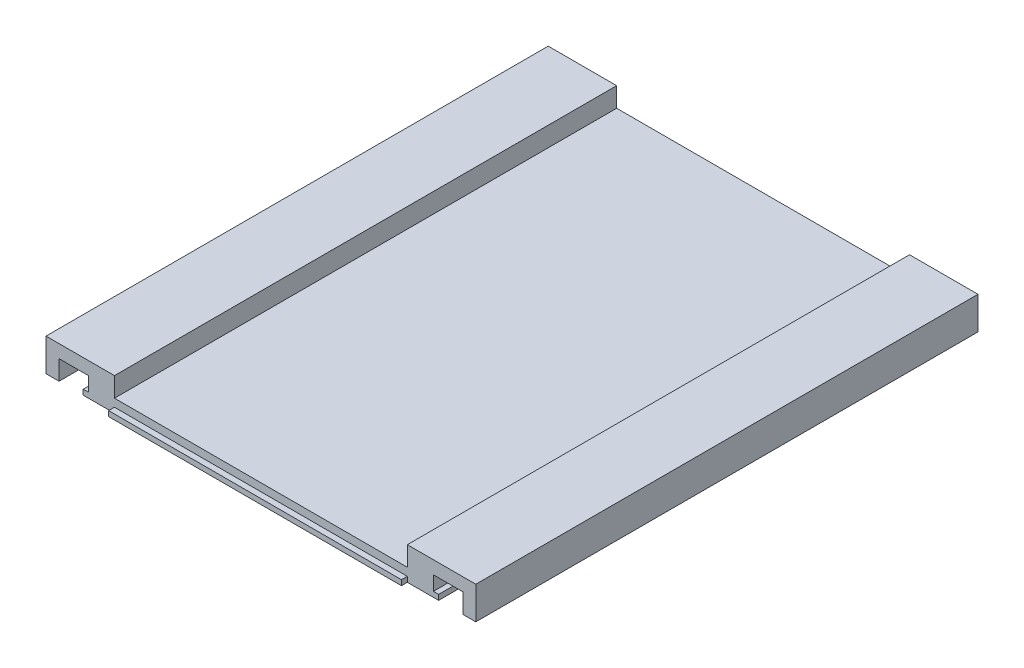
SolidWorks part; units mm, degrees
ref_plane "前视基准面" through (0, 0, 0) normal (0, 0, 1) x (1, 0, 0)
ref_plane "上视基准面" through (0, 0, 0) normal (0, 1, 0) x (1, 0, 0)
ref_plane "右视基准面" through (0, 0, 0) normal (1, 0, 0) x (0, 0, -1)
other "Configuration Table"
sketch "草图1" plane through (0, 0, 0) normal (0, 1, 0) x (1, 0, 0)
  line L0 (-26.45, 38.5) -> (-26.45, -38.5)
  line L1 (27.25, 38.5) -> (-27.25, 38.5)
  line L2 (27.25, 38.5) -> (27.25, -38.5)
  line L3 (27.25, -38.5) -> (-27.25, -38.5)
  line L4 (-27.25, 38.5) -> (-27.25, -38.5)
  line L5 (27.25, 38.5) -> (-27.25, -38.5) construction
  line L6 (27.25, -38.5) -> (-27.25, 38.5) construction
  line L7 (26.45, 38.5) -> (26.45, -38.5)
  point P0 (0, 0)
  dimension "D1" = 54.5
  dimension "D2" = 77
  dimension "D3" = 0.8
  dimension "D4" = 0.8
extrude "凸台-拉伸1" add sketch "草图1" along normal blind 2 contours L7 L1 L0 L3 region at (0, 0, 0)
extrude "凸台-拉伸2" add sketch "草图1<3>" along normal blind 0.8 contours L1 L7 L3 L2 | L1 L4 L3 L0 region at (-26.85, 0, 0) region at (26.85, 0, 0)
sketch "草图1<3>" plane through (0, 0, 0) normal (0, 1, 0) x (1, 0, 0) same geometry as "草图1"
sketch "草图2" plane through (0, 0, 0) normal (0, 1, 0) x (1, 0, 0)
  line L0 (-27.25, -38.5) -> (-27.25, -39.4)
  line L1 (-27.25, -39.4) -> (27.25, -39.4)
  line L2 (27.25, -39.4) -> (27.25, -38.5)
  line L3 (27.25, -38.5) -> (-27.25, -38.5)
  dimension "D1" = 0.9
extrude "凸台-拉伸3" add sketch "草图2" along normal blind 0.8
sketch "草图3" plane through (0, 0, 0) normal (0, 1, 0) x (1, 0, 0)
  line L0 (-27.25, -38.5) -> (-22.45, -38.5)
  line L1 (-27.25, 38.5) -> (-27.25, -39.4) construction
  line L2 (26.45, -38.5) -> (-26.45, -38.5) construction
  line L3 (-22.45, -38.5) -> (-22.45, -39.4)
  line L4 (-27.25, -39.4) -> (27.25, -39.4) construction
  line L5 (-22.45, -39.4) -> (-27.25, -39.4)
  line L6 (-27.25, -39.4) -> (-27.25, -38.5)
  line L7 (27.25, -38.5) -> (22.45, -38.5)
  line L8 (27.25, 38.5) -> (27.25, -39.4) construction
  line L9 (22.45, -38.5) -> (22.45, -39.4)
  line L10 (22.45, -39.4) -> (27.25, -39.4)
  line L11 (27.25, -39.4) -> (27.25, -38.5)
  dimension "D1" = 4.8
  dimension "D2" = 4.8
extrude "切除-拉伸1" cut sketch "草图3" along normal blind 0.8
sketch "草图4" plane through (0, 0, 0) normal (0, 0, 1) x (1, 0, 0)
  line L0 (22.45, 3) -> (22.45, 5)
  line L2 (22.45, 5) -> (32.95, 5)
  line L3 (32.95, 5) -> (32.95, 0)
  line L4 (32.95, 0) -> (30.95, 0)
  line L5 (30.95, 0) -> (30.95, 3)
  line L6 (30.95, 3) -> (26.45, 3)
  line L7 (0, 0) -> (0, -50000) construction
  line L8 (-30.95, 0) -> (-30.95, 3)
  line L9 (-30.95, 3) -> (-26.45, 3)
  line L10 (-32.95, 0) -> (-30.95, 0)
  line L11 (-32.95, 5) -> (-32.95, 0)
  line L12 (-22.45, 5) -> (-32.95, 5)
  line L13 (-22.45, 3) -> (-22.45, 5)
  line L15 (22.45, 3) -> (22.45, 2)
  line L16 (26.45, 2) -> (-26.45, 2) construction
  line L17 (22.45, 2) -> (26.45, 2)
  line L18 (26.45, 2) -> (26.45, 0.8) construction
  line L19 (26.45, 2) -> (26.45, 3)
  line L20 (-26.45, 2) -> (-26.45, 3)
  line L21 (-22.45, 2) -> (-26.45, 2)
  line L22 (-22.45, 3) -> (-22.45, 2)
  dimension "D1" = 2
  dimension "D2" = 2
  dimension "D3" = 3
  dimension "D4" = 4.5
  dimension "D5" = 1
extrude "凸台-拉伸4" add sketch "草图4" along normal up to surface (38.5 mm away) and the other way up to surface (38.5 mm away) up to face at (0, 0.7333, 38.5) other way up to face at (0, 0.9, -38.5)
